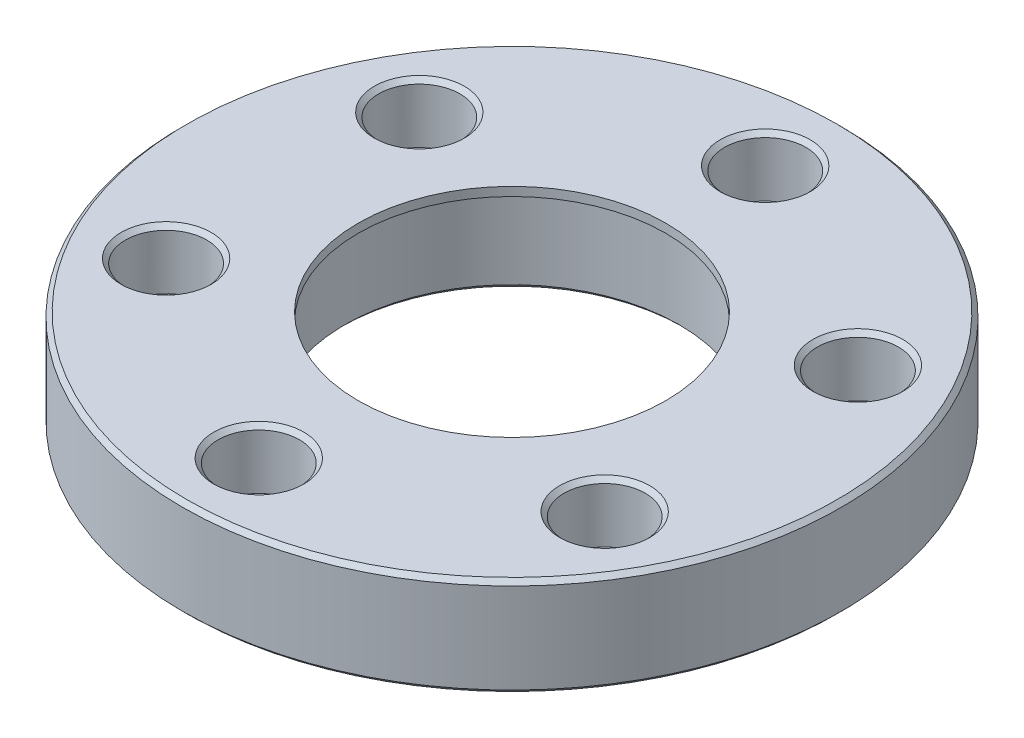
SolidWorks part; units mm, degrees
ref_plane "前视基准面" through (0, 0, 0) normal (0, 0, 1) x (1, 0, 0)
ref_plane "上视基准面" through (0, 0, 0) normal (0, 1, 0) x (1, 0, 0)
ref_plane "右视基准面" through (0, 0, 0) normal (1, 0, 0) x (0, 0, -1)
other "Configuration Table"
sketch "草图1" plane through (0, 0, 0) normal (0, 1, 0) x (1, 0, 0)
  circle A0 centre (0, 0) radius 7
  circle A1 centre (0, 0) radius 15
  circle A2 centre (0, 0) radius 11.525 construction
  circle A3 centre (0, 11.525) radius 1.85
  circle A4 centre (9.9809, 5.7625) radius 1.85
  circle A5 centre (9.9809, -5.7625) radius 1.85
  circle A6 centre (0, -11.525) radius 1.85
  circle A7 centre (-9.9809, -5.7625) radius 1.85
  circle A8 centre (-9.9809, 5.7625) radius 1.85
  point P19 (0, 0)
  dimension "D1" = 14
  dimension "D2" = 30
  dimension "D3" = 23.05
  dimension "D4" = 3.7
  dimension "D5" = 6
extrude "凸台-拉伸1" add sketch "草图1" along normal blind 2.7
sketch "草图2" plane through (0, 0, 0) normal (0, -1, 0) x (-1, 0, 0)
  circle A0 centre (0, 0) radius 7 construction
  circle A1 centre (0, 0) radius 15 construction
  circle A2 centre (0, 0) radius 7
  circle A3 centre (0, 0) radius 15
  circle A4 centre (0, 11.53) radius 0.9
  circle A6 centre (0, 0) radius 11.53 construction
  circle A7 centre (9.9853, 5.765) radius 0.9
  circle A8 centre (9.9853, -5.765) radius 0.9
  circle A9 centre (0, -11.53) radius 0.9
  circle A10 centre (-9.9853, -5.765) radius 0.9
  circle A11 centre (-9.9853, 5.765) radius 0.9
  point P21 (0, 0)
  dimension "D1" = 1.8
  dimension "D2" = 23.06
  dimension "D3" = 6
extrude "凸台-拉伸2" add sketch "草图2" along normal blind 1.8
sketch "草图3" plane through (0, -1.8, 0) normal (0, -1, 0) x (-1, 0, 0)
  circle A0 centre (0, 0) radius 7.6
  dimension "D1" = 15.2
extrude "切除-拉伸1" cut sketch "草图3" against normal blind 4.1
chamfer "倒角1" distance 0.2 angle 45 15 edges at (0, -1.8, -15) (-9.9809, 2.7, -3.9125) (0, 2.7, 13.375) (9.9809, 2.7, -3.9125) (0, 2.7, 15) (0, 2.7, -9.675) (9.9809, 2.7, 7.6125) (-9.9809, 2.7, 7.6125) (9.9853, -1.8, -6.665) (0, -1.8, 10.63) (-9.9853, -1.8, -6.665) (0, -1.8, -12.43) (-9.9853, -1.8, 4.865) (9.9853, -1.8, 4.865) (0, -1.8, -7.6)
chamfer "倒角2" distance 0.3 angle 45 1 edges at (0, 2.3, -7.6)
